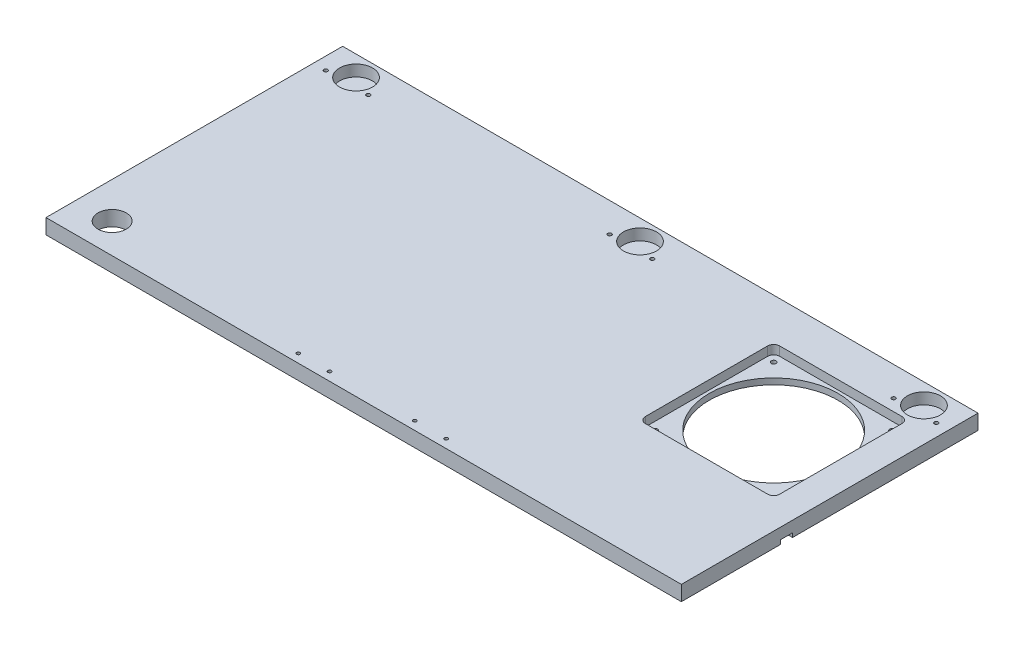
SolidWorks part; units mm, degrees
ref_plane "Front Plane" through (0, 0, 0) normal (0, 0, 1) x (1, 0, 0)
ref_plane "Top Plane" through (0, 0, 0) normal (0, 1, 0) x (1, 0, 0)
ref_plane "Right Plane" through (0, 0, 0) normal (1, 0, 0) x (0, 0, -1)
sketch "Sketch1" plane through (0, 0, 0) normal (0, 1, 0) x (1, 0, 0)
  line L1 (335.6356, 156.7053) -> (-335.6356, 156.7053)
  line L2 (335.6356, 156.7053) -> (335.6356, -156.7053)
  line L3 (335.6356, -156.7053) -> (-335.6356, -156.7053)
  line L4 (-335.6356, 156.7053) -> (-335.6356, -156.7053)
  line L5 (335.6356, 156.7053) -> (-335.6356, -156.7053) construction
  line L6 (335.6356, -156.7053) -> (-335.6356, 156.7053) construction
  point P0 (0, 0)
  dimension "D1" = 671.2712
  dimension "D2" = 313.4106
extrude "Boss-Extrude1" add sketch "Sketch1" along normal blind 15.875
sketch "Sketch2" plane through (0, 15.875, 0) normal (0, 1, 0) x (1, 0, 0)
  line L0 (335.6356, 156.7053) -> (-335.6356, 156.7053) construction
  line L1 (343.5731, 137.6553) -> (-343.5731, 137.6553)
  line L2 (343.5731, 137.6553) -> (343.5731, -137.6553)
  line L3 (343.5731, -137.6553) -> (-343.5731, -137.6553)
  line L4 (-343.5731, 137.6553) -> (-343.5731, -137.6553)
  line L5 (343.5731, 137.6553) -> (-343.5731, -137.6553) construction
  line L6 (343.5731, -137.6553) -> (-343.5731, 137.6553) construction
  line L7 (-335.6356, 156.7053) -> (-335.6356, -156.7053) construction
  point P0 (0, 0)
  dimension "D1" = 19.05
  dimension "D2" = 7.9375
extrude "Boss-Extrude2" [suppressed] add sketch "Sketch2" against normal up to surface (15.875 mm away) up to face at (0, 0, 0)
fillet "Fillet1" [suppressed] radius 6.35
sketch "Sketch4" plane through (0, 15.875, 0) normal (0, 1, 0) x (1, 0, 0)
  line L1 (0, 0) -> (0, -124.9553) construction
  line L2 (-335.6356, -156.7053) -> (335.6356, -156.7053) construction
  line L3 (-335.6356, 156.7053) -> (-335.6356, -156.7053) construction
  circle A1 centre (-297.5356, -124.9553) radius 14.9225
  dimension "D3" = 31.75
  dimension "D5" = 29.845
  dimension "D4" = 38.1
extrude "Cut-Extrude2" cut sketch "Sketch4" against normal through all both and the other way through all
sketch "Sketch5" plane through (0, 15.875, 0) normal (0, 1, 0) x (1, 0, 0)
  line L0 (0, 0) -> (0, 156.7053) construction
  line L1 (335.6356, 156.7053) -> (-335.6356, 156.7053) construction
  line L2 (-300, 135.2428) -> (-300, 146.2735) construction
  circle A0 centre (0, 135.2428) radius 17.4625
  circle A1 centre (22.5, 125.7428) radius 2
  circle A2 centre (-22.5, 125.7428) radius 2
  circle A3 centre (-300, 135.2428) radius 17.4625
  circle A4 centre (-277.5, 125.7428) radius 2
  circle A5 centre (-322.5, 125.7428) radius 2
  circle A6 centre (322.5, 125.7428) radius 2
  circle A7 centre (277.5, 125.7428) radius 2
  circle A8 centre (300, 135.2428) radius 17.4625
  dimension "D1" = 34.925
  dimension "D3" = 45
  dimension "D4" = 4
  dimension "D6" = 4
  dimension "D5" = 9.5
  dimension "D2" = 45
  dimension "D7" = 300
extrude "Cut-Extrude3" cut sketch "Sketch5" against normal blind 11.9062
sketch "Sketch6" plane through (0, 15.875, 0) normal (0, 1, 0) x (1, 0, 0)
  line L0 (-335.6356, -156.7053) -> (335.6356, -156.7053) construction
  line L1 (78.05, -147.7053) -> (45.05, -147.7053) construction
  line L2 (-45.05, -147.7053) -> (-78.05, -147.7053) construction
  circle A0 centre (78.05, -147.7053) radius 1.8
  circle A1 centre (45.05, -147.7053) radius 1.8
  circle A2 centre (-45.05, -147.7053) radius 1.8
  circle A4 centre (-78.05, -147.7053) radius 1.8
  point P8 (61.55, -147.7053)
  point P12 (-61.55, -147.7053)
  dimension "D2" = 3.6
  dimension "D3" = 33
  dimension "D1" = 9
  dimension "D4" = 33
  dimension "D5" = 61.55
  dimension "D6" = 61.55
extrude "Cut-Extrude4" cut sketch "Sketch6" against normal blind 2.54
sketch "Sketch7" plane through (0, 15.875, 0) normal (0, 1, 0) x (1, 0, 0)
  line L2 (335.6356, 156.7053) -> (-335.6356, 156.7053) construction
  line L3 (335.6356, -156.7053) -> (335.6356, 156.7053) construction
  circle A0 centre (234.0356, 42.4053) radius 68
  circle A1 centre (296.5356, -20.0947) radius 2.54
  circle A2 centre (296.5356, 104.9053) radius 2.54
  circle A3 centre (171.5356, 104.9053) radius 2.54
  circle A4 centre (171.5356, -20.0947) radius 2.54
  circle A5 centre (234.0356, 42.4053) radius 88.3883 construction
  dimension "D1" = 125
  dimension "D2" = 125
  dimension "D3" = 5.08
  dimension "D4" = 136
  dimension "D5" = 114.3
  dimension "D6" = 101.6
extrude "Cut-Extrude5" cut sketch "Sketch7" against normal through all both and the other way through all
sketch "Sketch8" plane through (0, 15.875, 0) normal (0, 1, 0) x (1, 0, 0)
  line L1 (169.3856, -28.5947) -> (298.6856, -28.5947)
  line L2 (163.0356, -22.2447) -> (163.0356, 107.0553)
  line L3 (169.3856, 113.4053) -> (298.6856, 113.4053)
  line L4 (305.0356, -22.2447) -> (305.0356, 107.0553)
  line L5 (163.0356, -28.5947) -> (305.0356, 113.4053) construction
  line L6 (163.0356, 113.4053) -> (305.0356, -28.5947) construction
  arc A0 (163.0356, 107.0553) -> (169.3856, 113.4053) centre (169.3856, 107.0553) cw
  arc A1 (298.6856, 113.4053) -> (305.0356, 107.0553) centre (298.6856, 107.0553) cw
  arc A2 (298.6856, -28.5947) -> (305.0356, -22.2447) centre (298.6856, -22.2447) ccw
  arc A3 (169.3856, -28.5947) -> (163.0356, -22.2447) centre (169.3856, -22.2447) cw
  point P0 (234.0356, 42.4053)
  dimension "D3" = 6.35
  dimension "D1" = 142
  dimension "D2" = 142
extrude "Cut-Extrude6" cut sketch "Sketch8" against normal blind 9.525
sketch "Sketch9" plane through (0, 0, 0) normal (0, -1, 0) x (1, 0, 0)
  line L0 (335.6356, 156.7053) -> (335.6356, -156.7053) construction
  line L1 (335.6356, 39.2303) -> (-335.6356, 39.2303)
  line L2 (335.6356, 39.2303) -> (335.6356, 51.7303)
  line L3 (335.6356, 51.7303) -> (-335.6356, 51.7303)
  line L4 (-335.6356, 39.2303) -> (-335.6356, 51.7303)
  line L5 (-335.6356, -156.7053) -> (-335.6356, 156.7053) construction
  line L6 (-335.6356, 156.7053) -> (335.6356, 156.7053) construction
  dimension "D1" = 12.5
  dimension "D2" = 117.475
extrude "Cut-Extrude7" cut sketch "Sketch9" against normal blind 4.35
